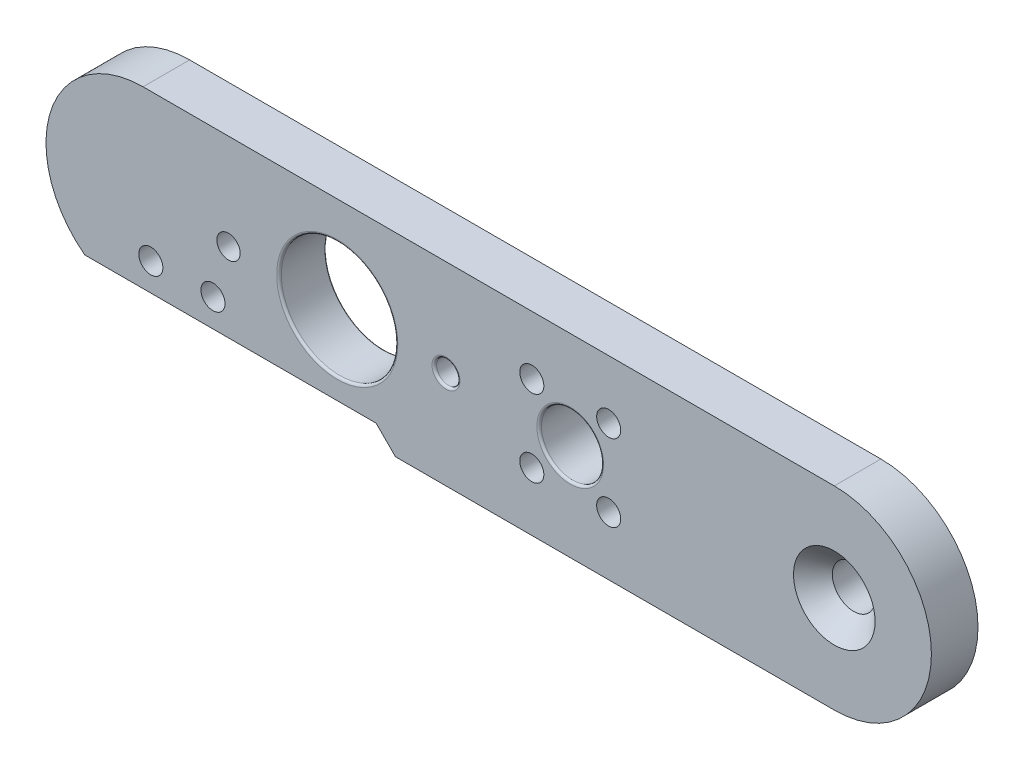
SolidWorks part; units mm, degrees
material "Stainless Steel (ferritic)"
ref_plane "Front Plane" through (0, 0, 0) normal (0, 0, 1) x (1, 0, 0)
ref_plane "Top Plane" through (0, 0, 0) normal (0, 1, 0) x (1, 0, 0)
ref_plane "Right Plane" through (0, 0, 0) normal (1, 0, 0) x (0, 0, -1)
sketch "Sketch2" plane through (0, 0, 0) normal (0, 0, 1) x (1, 0, 0)
  line L0 (-44.5, 0) -> (44.5, 0) construction
  line L1 (-44.5, 12.5) -> (44.5, 12.5)
  line L2 (-44.5, -12.5) -> (44.5, -12.5)
  arc A0 (-44.5, 12.5) -> (-44.5, -12.5) centre (-44.5, 0) ccw
  arc A1 (44.5, -12.5) -> (44.5, 12.5) centre (44.5, 0) ccw
  point P2 (0, 0)
  point P8 (-57, 0)
  point P9 (57, 0)
  dimension "D2" = 12.5
  dimension "D1" = 114
extrude "Boss-Extrude1" add sketch "Sketch2" along normal blind 6
sketch "Sketch4" plane through (0, 0, 6) normal (0, 0, 1) x (1, 0, 0)
  line L0 (-52, -10) -> (-26.9514, -10)
  line L7 (-12, -12.5) -> (-12, -21.3289)
  line L8 (44.5, 12.5) -> (44.5, -12.5)
  line L9 (10.5, 0) -> (10.5, -25.6152)
  line L10 (44.5, 12.5) -> (-44.5, 12.5) construction
  line L11 (10.5, -10) -> (-14.5, -10)
  line L12 (-26.9514, -10) -> (-14.5, -10)
  line L13 (10.5, 0) -> (10.5, 11.9292)
  line L14 (-44.5, -12.5) -> (44.5, -12.5) construction
  line L16 (-14.5, -10) -> (-12, -12.5)
  line L17 (-52, -10) -> (-52, -20.7157)
  line L18 (-52, -20.7157) -> (-12, -21.3289)
  circle A0 centre (10.5, 0) radius 4
  circle A3 centre (5.5503, 4.9497) radius 1.55
  circle A10 centre (-19.5, 0.1762) radius 7.5
  arc A11 (-44.5, 12.5) -> (-44.5, -12.5) centre (-44.5, 0) ccw construction
  arc A12 (44.5, -12.5) -> (44.5, 12.5) centre (44.5, 0) ccw construction
  circle A13 centre (15.4497, 4.9497) radius 1.55
  circle A14 centre (15.4497, -4.9497) radius 1.55
  circle A15 centre (5.5503, -4.9497) radius 1.55
  point P2 (44.5, 0)
  point P43 (10.5, 0)
  arc M1 (-44.5, 12.5) -> (-44.5, -12.5) centre (-44.5, 0) ccw
  line M4 (-44.5, -12.5) -> (44.5, -12.5)
  dimension "D1" = 8
  dimension "D3" = 15
  dimension "D4" = 3.1
  dimension "D5" = 30
  dimension "D2" = 4
  dimension "D7" = 22.5
  dimension "D8" = 25
  dimension "D10" = 34
extrude "Cut-Extrude2" cut sketch "Sketch4" against normal blind 6 contours L16 L12 L0 M1 M4 region at (-31.4646, -11.2305, 6)
extrude "Cut-Extrude3" cut sketch "Sketch4<3>" against normal blind 6 contours A10 | A13 | A14 | A15 | A0 | A3 region at (-19.5, 0.1762, 6) region at (15.4497, 4.9497, 6) region at (15.4497, -4.9497, 6) region at (5.5503, -4.9497, 6)
sketch "Sketch4<3>" plane through (0, 0, 6) normal (0, 0, 1) x (1, 0, 0) same geometry as "Sketch4"
sketch "Sketch6" plane through (0, 0, 6) normal (0, 0, 1) x (1, 0, 0)
  point P0 (-5.5002, 0.0828)
  point P2 (-33.5, 0.1762)
  point P5 (-19.5, 0.1762)
  dimension "D1" = 28
  dimension "D2" = 14
hole_wizard "Ø3.0mm Dowel Hole1" positions "Sketch6" profile "Sketch7" hole size "Ø3.0" standard "ANSI Metric" end condition through all
sketch "Sketch7" plane through (-5.5002, 0.0828, 6) normal (1, 0, 0) x (0, -1, 0)
  line L0 (0, 0) -> (0, 6)
  line L1 (0, 6) -> (1.5, 6)
  line L2 (1.5, 6) -> (1.5, 0)
  line L5 (1.5, 0) -> (0, 0)
  line L11 (0, -6.35) -> (0, 107.95) construction
  dimension "Thru Hole Dia." = 3
  dimension "Thru Hole Depth" = 6
sketch "Sketch8" plane through (0, 0, 6) normal (0, 0, 1) x (1, 0, 0)
  circle A0 centre (-43.5, -6.4137) radius 1.55
  circle A1 centre (-35.5, -6.4137) radius 1.55
  point P4 (-19.5, 0.1762)
  dimension "D1" = 3.1
  dimension "D2" = 3.1
  dimension "D3" = 8
  dimension "D4" = 16
extrude "Cut-Extrude4" cut sketch "Sketch8" against normal blind 3
sketch "Sketch9" plane through (0, 0, 3) normal (0, 0, 1) x (1, 0, 0)
  circle A0 centre (-43.5, -6.4137) radius 3
  circle A1 centre (-35.5, -6.4137) radius 3
  dimension "D1" = 6
  dimension "D2" = 6
extrude "Cut-Extrude5" cut sketch "Sketch9" against normal blind 3
sketch "Sketch18" plane through (0, 0, 6) normal (0, 0, 1) x (1, 0, 0)
  point P0 (44.5, 0)
hole_wizard "CSK for M5 Flat Head Machine Screw2" positions "Sketch18" profile "Sketch19" countersink size "M5" standard "ANSI Metric" end condition through all
sketch "Sketch19" plane through (44.5, 0, 6) normal (1, 0, 0) x (0, -1, 0)
  line L0 (0, 0) -> (0, 6)
  line L1 (0, 6) -> (2.75, 6)
  line L2 (2.75, 6) -> (2.75, 2.5)
  line L3 (2.75, 2.5) -> (5.25, 0)
  line L5 (5.25, 0) -> (0, 0)
  line L6 (-2.75, 2.5) -> (-5.25, 0) construction
  line L11 (0, -6.35) -> (0, 107.95) construction
  dimension "Thru Hole Dia." = 5.5
  dimension "Thru Hole Depth" = 6
  dimension "Near C'Sink Dia." = 10.5
  dimension "Near C'Sink Angle" = 90
fillet "Fillet1" radius 0.1 2 edges at (-12, 0.1762, 0) (14.5, 0, 0)
fillet "Fillet2" radius 0.3 4 edges at (14.5, 0, 6) (-4.0002, 0.0828, 6) (-4.0002, 0.0828, 0) (-12, 0.1762, 6)
